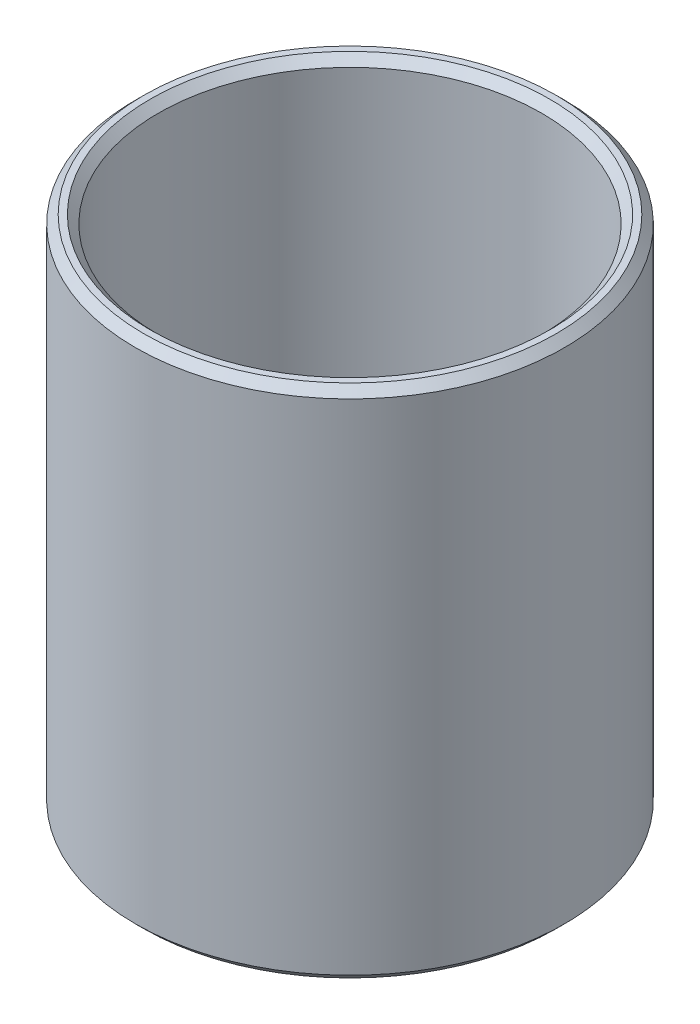
SolidWorks part; units mm, degrees
ref_plane "Front Plane" through (0, 0, 0) normal (0, 0, 1) x (1, 0, 0)
ref_plane "Top Plane" through (0, 0, 0) normal (0, 1, 0) x (1, 0, 0)
ref_plane "Right Plane" through (0, 0, 0) normal (1, 0, 0) x (0, 0, -1)
sketch "Sketch1" plane through (0, 0, 0) normal (0, 1, 0) x (1, 0, 0)
  circle A0 centre (0, 0) radius 42.5
  dimension "SLEEVE_OD" = 85
extrude "Boss-Extrude1" add sketch "Sketch1" along normal blind 102.1039
sketch "Sketch2" plane through (0, 0, 0) normal (0, 1, 0) x (1, 0, 0)
  circle A0 centre (0, 0) radius 37.9929
  dimension "BORE_D" = 75.9859
extrude "Cut-Extrude1" cut sketch "Sketch2" along normal through all
chamfer "Chamfer1" distance 1.6074 angle 45 4 edges at (0, 102.1039, 37.9929) (0, 0, 37.9929) (0, 0, 42.5) (0, 102.1039, 42.5)
